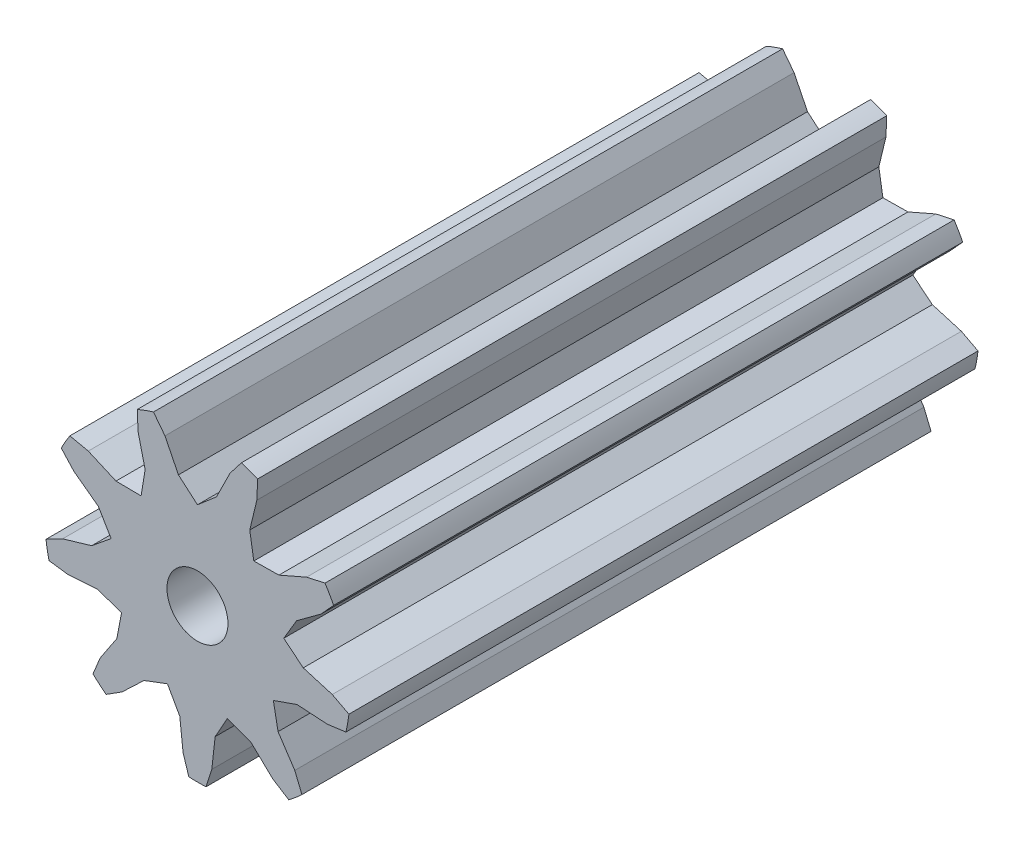
SolidWorks part; units mm, degrees
ref_plane "Front Plane" through (0, 0, 0) normal (0, 0, 1) x (1, 0, 0)
ref_plane "Top Plane" through (0, 0, 0) normal (0, 1, 0) x (1, 0, 0)
ref_plane "Right Plane" through (0, 0, 0) normal (1, 0, 0) x (0, 0, -1)
sketch "Sketch1" plane through (0, 0, 0) normal (0, 0, 1) x (1, 0, 0)
  line L1 (1.2374, -1.2374) -> (-1.2374, -1.2374) construction
  line L2 (1.2374, -1.2374) -> (1.2374, 1.2374) construction
  line L3 (1.2374, 1.2374) -> (-1.2374, 1.2374) construction
  line L4 (-1.2374, -1.2374) -> (-1.2374, 1.2374) construction
  line L5 (1.2374, -1.2374) -> (-1.2374, 1.2374) construction
  line L6 (1.2374, 1.2374) -> (-1.2374, -1.2374) construction
  circle A0 centre (0, 0) radius 8
  circle A1 centre (0, 0) radius 1.75 construction
  dimension "D1" = 16
  dimension "D2" = 3.5
extrude "Boss-Extrude1" add sketch "Sketch1" along normal blind 33
sketch "Sketch2" plane through (0, 0, 0) normal (0, 0, 1) x (1, 0, 0)
  line L0 (0, 0) -> (0, 10.088) construction
  line L1 (0, 4.5987) -> (-0.9985, 5.4581)
  line L8 (-1.7043, 8.4435) -> (0, 9.1577)
  line L11 (-0.9985, 5.4581) -> (-1.7043, 6.8791)
  line L12 (-1.7043, 6.8791) -> (-2.3066, 7.6603)
  line L13 (-2.3066, 7.6603) -> (-1.7043, 8.4435)
  line L14 (2.3066, 7.6603) -> (1.7043, 8.4435)
  line L15 (1.7043, 6.8791) -> (2.3066, 7.6603)
  line L16 (0.9985, 5.4581) -> (1.7043, 6.8791)
  line L17 (1.7043, 8.4435) -> (0, 9.1577)
  line L18 (0, 4.5987) -> (0.9985, 5.4581)
  circle A14 centre (0, 0) radius 8 construction
  point P16 (0, 8)
  dimension "D5" = 0.6023
  dimension "D6" = 0.7811
  dimension "D1" = 0.9985
  dimension "D2" = 0.8594
  dimension "D3" = 0.7058
  dimension "D4" = 1.4211
  dimension "D7" = 0.7832
  dimension "D8" = 0.6023
  dimension "D9" = 0.7142
  dimension "D10" = 1.7043
extrude "Cut-Extrude1" cut sketch "Sketch2" along normal through all
sketch "Sketch3" plane through (0, 0, 0) normal (0, 0, 1) x (1, 0, 0)
  circle A0 centre (0, 0) radius 7.5
  dimension "D1" = 15
sketch "Sketch4" plane through (0, 0, 33) normal (0, 0, 1) x (1, 0, 0)
  circle A0 centre (0, 0) radius 1.6
  dimension "D1" = 3.2
extrude "Cut-Extrude2" cut sketch "Sketch4" against normal through all both and the other way through all
pattern_circular "CirPattern1" count 9 over 360 about axis through (0, 0, 33) along (0, 0, -1) of "Cut-Extrude1" reverse direction yes
sketch "Sketch5" plane through (0, 0, 0) normal (0, 0, 1) x (1, 0, 0)
  line L0 (0, 0) -> (0, 16.5734) construction
  arc A0 (0, 2.7703) -> (-2.7395, 5.5802) centre (3.9333, 9.3453) cw
  arc A1 (-2.7395, 5.5802) -> (0, 7.0858) centre (3.4783, -2.4876) cw
  arc A2 (2.7395, 5.5802) -> (0, 7.0858) centre (-3.4783, -2.4876) ccw
  arc A3 (0, 2.7703) -> (2.7395, 5.5802) centre (-3.9333, 9.3453) ccw
equation "\"circle\"=16"
equation "\"D1@Sketch1\"=\"circle\""
equation "\"separator_width\"=45"
equation "\"big-gear-thiccness\"=2"
equation "\"D1@Boss-Extrude1\"=\"separator_width\" - \"big-gear-thiccness\"-10"
